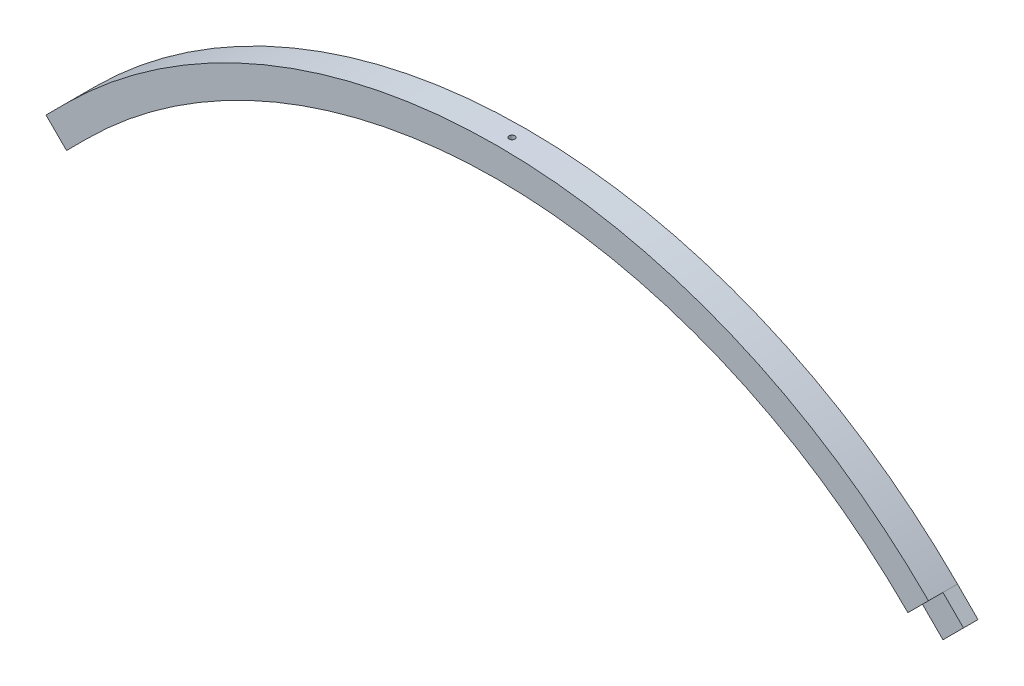
SolidWorks part; units mm, degrees
ref_plane "Ön Düzlem" through (0, 0, 0) normal (0, 0, 1) x (1, 0, 0)
ref_plane "Üst Düzlem" through (0, 0, 0) normal (0, 1, 0) x (1, 0, 0)
ref_plane "Sağ Düzlem" through (0, 0, 0) normal (1, 0, 0) x (0, 0, -1)
sketch "Çizim1" plane through (0, 0, 0) normal (0, 0, 1) x (1, 0, 0)
  circle A0 centre (0, 0) radius 200
  circle A1 centre (0, 0) radius 210
extrude "Yükseklik-Ekstrüzyon1" add sketch "Çizim1" along normal blind 10
sketch "Çizim3" plane through (0, 0, 0) normal (0, 1, 0) x (1, 0, 0)
  line L0 (0, 0) -> (0, -10)
  line L1 (-210, -10) -> (210, -10) construction
  circle A0 centre (0, -5) radius 1
extrude "Kes-Ekstrüzyon1" cut sketch "Çizim3" against normal blind 290 and the other way blind 290 contours L0 A0 | L0 A0 region at (0.4244, 0, 5) region at (-0.4244, 0, 5)
sketch "Çizim4" plane through (0, 0, 0) normal (1, 0, 0) x (0, 0, -1)
  line L0 (-10, 0) -> (0, 0)
  line L1 (-10, 210) -> (-10, -210) construction
  circle A0 centre (-5, 0) radius 1
extrude "Kes-Ekstrüzyon2" cut sketch "Çizim4" against normal blind 290 and the other way blind 290 contours L0 A0 | L0 A0 region at (0, 0.4244, 5) region at (0, -0.4244, 5)
sketch "Çizim5" plane through (0, 0, 0) normal (0, 0, 1) x (1, 0, 0)
  line L0 (-250, 250) -> (250, -250)
  line L1 (-250, 250) -> (250, 250)
  line L2 (-250, 250) -> (-250, -250)
  line L3 (-250, -250) -> (250, -250)
  line L4 (250, 250) -> (250, -250)
  line L5 (-250, 250) -> (250, -250) construction
  line L6 (-250, -250) -> (250, 250) construction
  line L7 (250, 250) -> (-250, -250)
  line L8 (-250, 250) -> (250, -250)
  line L9 (250, 250) -> (-250, -250)
  circle A0 centre (0, 0) radius 210
  circle A1 centre (0, 0) radius 200
  point P0 (0, 0)
extrude "Kes-Ekstrüzyon8" cut sketch "Çizim5" against normal blind 455 and the other way blind 184 contours A1 L8 A0 L9 | A1 L8 A0 L9 | A1 L9 A0 L8 region at (-147.1122, 142.8016, 0) region at (191.1987, 79.1971, 0) region at (-142.8016, -147.1122, 0)
sketch "Çizim6" plane through (0, 0, 0) normal (0.7071, -0.7071, 0) x (0, 0, -1)
  line L0 (-10, 210) -> (0, 210)
  line L1 (0, 210) -> (0, 200)
  line L2 (0, 200) -> (-10, 200)
  line L3 (-10, 200) -> (-10, 210)
  line L4 (-5, 210) -> (-5, 200)
  line M6 (0, 200) -> (0, 210)
  line M7 (0, 210) -> (-10, 210)
extrude "Yükseklik-Ekstrüzyon2" add sketch "Çizim6" along normal blind 10 contours L4 L2 M7 M6 region at (144.9569, 144.9569, 2.5)
sketch "Çizim7" plane through (0, 0, 0) normal (-0.7071, -0.7071, 0) x (0, 0, 1)
  line L0 (0, 210) -> (10, 210)
  line L1 (10, 210) -> (10, 200)
  line L2 (10, 200) -> (0, 200)
  line L3 (0, 200) -> (0, 210)
  line L4 (5, 210) -> (5, 200)
  line M5 (10, 200) -> (10, 210)
  line M6 (10, 210) -> (0, 210)
extrude "Yükseklik-Ekstrüzyon4" add sketch "Çizim7" along normal blind 10 contours L4 L2 M6 M5 region at (-144.9569, 144.9569, 7.5)
